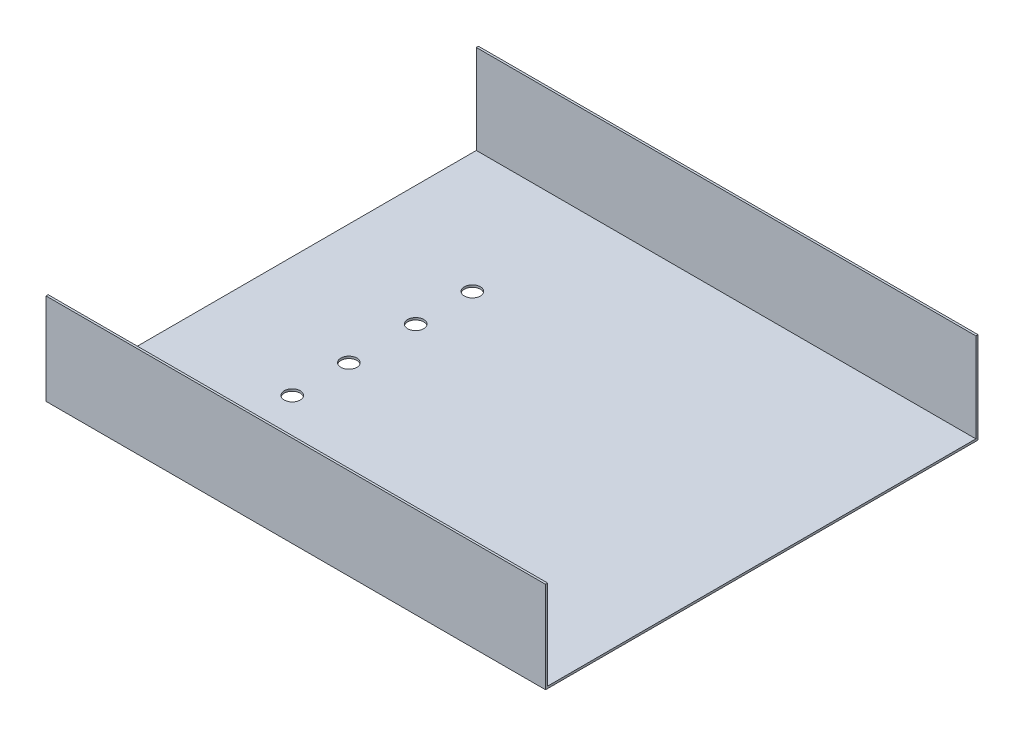
SolidWorks part; units mm, degrees
material "AISI 304"
ref_plane "Alzado" through (0, 0, 0) normal (0, 0, 1) x (1, 0, 0)
ref_plane "Planta" through (0, 0, 0) normal (0, 1, 0) x (1, 0, 0)
ref_plane "Vista lateral" through (0, 0, 0) normal (1, 0, 0) x (0, 0, -1)
sketch "Croquis1" plane through (0, 0, 0) normal (1, 0, 0) x (0, 0, -1)
  line L0 (0, 25) -> (0, 0)
  line L1 (0, 0) -> (120, 0)
  line L2 (120, 0) -> (120, 25)
  line L3 (0, 25) -> (120, 25)
  dimension "D1" = 120
  dimension "D2" = 25
extrude "Saliente-Extruir1" add sketch "Croquis1" along normal blind 140
shell "Vaciado1" thickness 0.6 removed face at (0, 12.5, -60) removed face at (140, 12.5, -60) removed face at (70, 25, -60) outward yes
hole_wizard "Taladro de margen para M41" positions "Croquis2" profile "Croquis3" hole size "M4" standard "Ansi Metric"
sketch "Croquis2" plane through (83.2595, 0, -172.6309) normal (0, 1, 0) x (1, 0, 0)
  point P0 (-49.6095, -137.8684)
  point P3 (-49.6095, -87.3934)
  point P6 (-49.6095, -103.2684)
  point P11 (-49.6095, -121.9934)
sketch "Croquis3" plane through (33.65, 0, -34.7625) normal (1, 0, 0) x (0, 0, 1)
  line L0 (0, 0) -> (0, 0.599)
  line L1 (0, 0.599) -> (2.25, 0.599)
  line L2 (2.25, 0.599) -> (2.25, 0)
  line L5 (2.25, 0) -> (0, 0)
  line L11 (0, -6.35) -> (0, 107.95) construction
  dimension "Diámetro de taladro hasta el siguiente" = 4.5
  dimension "Profundidad de taladro hasta el siguiente" = 0.599
